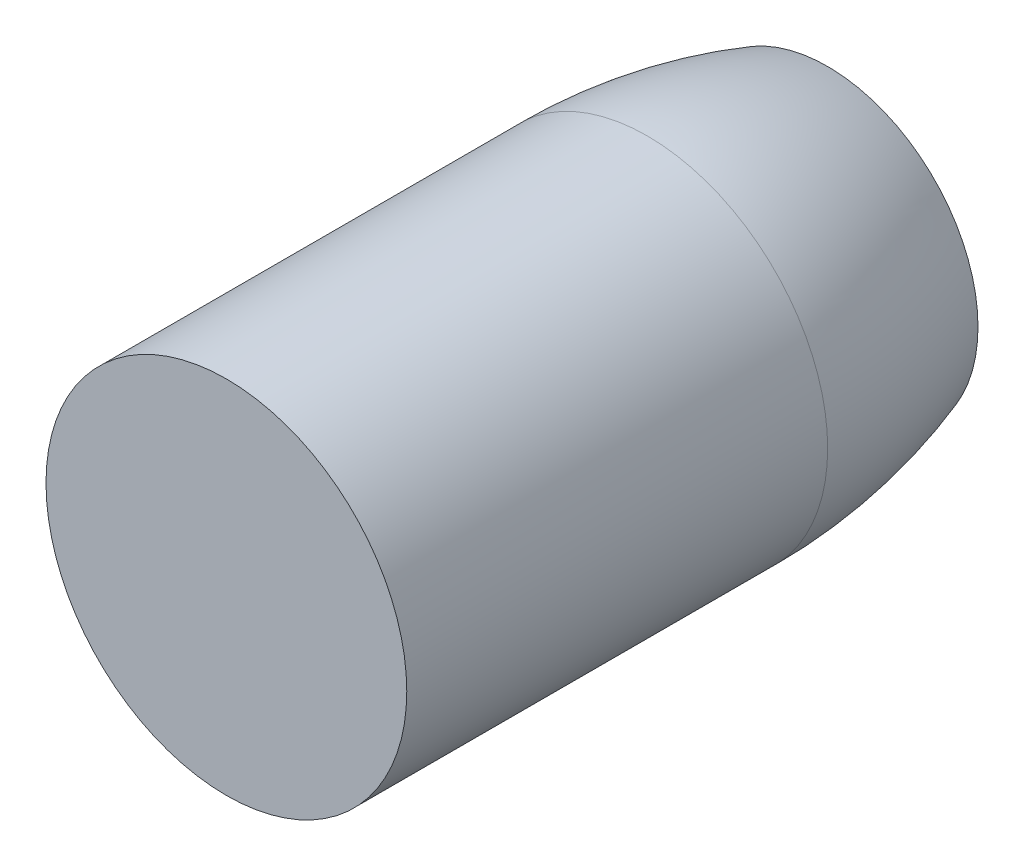
SolidWorks part; units mm, degrees
ref_plane "Top Plane" through (0, 0, 0) normal (0, 0, 1) x (1, 0, 0)
ref_plane "Front Plane" through (0, 0, 0) normal (0, 1, 0) x (1, 0, 0)
ref_plane "Right Plane" through (0, 0, 0) normal (1, 0, 0) x (0, 0, -1)
sketch "Sketch1" plane through (0, 0, 0) normal (0, 1, 0) x (1, 0, 0)
  line L0 (0, 0) -> (0, 14.2832) construction
  line L1 (0, 0) -> (6, 0)
  line L2 (6, 0) -> (6, 14)
  line L3 (5, 20) -> (4.75, 20)
  line L4 (4.75, 20) -> (4.75, 17)
  line L5 (4.75, 17) -> (0, 17)
  line L6 (0, 17) -> (0, 0)
  arc A0 (6, 14) -> (5, 20) centre (-12.5, 14) ccw
  point P7 (0, 0)
  dimension "D1" = 6
  dimension "D2" = 14
  dimension "D3" = 6
  dimension "D4" = 0.25
  dimension "D5" = 1
  dimension "D6" = 3
revolve "Revolve1" add sketch "Sketch1" angle 360 about L0
ref_axis "Axis1" through (0, 0, -14) along (0, 0, 1)
